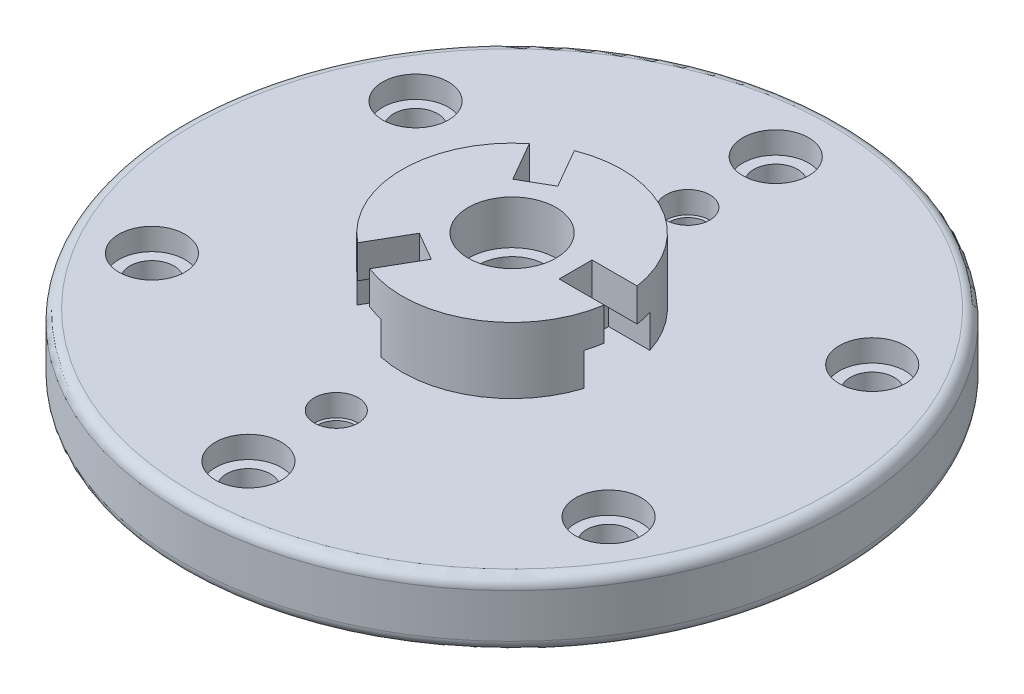
SolidWorks part; units mm, degrees
ref_plane "Front Plane" through (0, 0, 0) normal (0, 0, 1) x (1, 0, 0)
ref_plane "Top Plane" through (0, 0, 0) normal (0, 1, 0) x (1, 0, 0)
ref_plane "Right Plane" through (0, 0, 0) normal (1, 0, 0) x (0, 0, -1)
sketch "Sketch1" plane through (0, 0, 0) normal (0, 1, 0) x (1, 0, 0)
  circle A0 centre (0, 0) radius 30
  dimension "D1" = 60
extrude "Boss-Extrude1" add sketch "Sketch1" along normal blind 50
sketch "Sketch2" plane through (0, 50, 0) normal (0, 1, 0) x (1, 0, 0)
  circle A0 centre (0, 0) radius 60
  dimension "D1" = 120
extrude "Boss-Extrude2" add sketch "Sketch2" along normal blind 20
sketch "Sketch3" plane through (0, 70, 0) normal (0, 1, 0) x (1, 0, 0)
  circle A0 centre (0, 0) radius 150
  dimension "D1" = 300
extrude "Boss-Extrude3" add sketch "Sketch3" along normal blind 30
sketch "Sketch4" plane through (0, 100, 0) normal (0, 1, 0) x (1, 0, 0)
  circle A0 centre (0, 0) radius 50
  dimension "D1" = 100
extrude "Boss-Extrude4" add sketch "Sketch4" along normal blind 30
sketch "Sketch5" plane through (0, 130, 0) normal (0, 1, 0) x (1, 0, 0)
  circle A0 centre (0, 0) radius 15
  dimension "D1" = 30
extrude "Cut-Extrude1" cut sketch "Sketch5" against normal through all
sketch "Sketch6" plane through (0, 130, 0) normal (0, 1, 0) x (1, 0, 0)
  circle A0 centre (0, 0) radius 20
  dimension "D1" = 40
extrude "Cut-Extrude2" cut sketch "Sketch6" against normal blind 20
sketch "Sketch7" plane through (0, 100, 0) normal (0, 1, 0) x (1, 0, 0)
  circle A0 centre (0, 0) radius 120 construction
  circle A1 centre (0, 120) radius 15
  circle A2 centre (0, 120) radius 10
  circle A3 centre (103.923, 60) radius 15
  circle A4 centre (103.923, 60) radius 10
  circle A5 centre (103.923, -60) radius 15
  circle A6 centre (103.923, -60) radius 10
  circle A7 centre (0, -120) radius 15
  circle A8 centre (0, -120) radius 10
  circle A9 centre (-103.923, -60) radius 15
  circle A10 centre (-103.923, -60) radius 10
  circle A11 centre (-103.923, 60) radius 15
  circle A12 centre (-103.923, 60) radius 10
  point P24 (0, 0)
  dimension "D1" = 240
  dimension "D2" = 30
  dimension "D3" = 20
  dimension "D4" = 6
extrude "Cut-Extrude3" cut sketch "Sketch7" against normal blind 10 contours A10 | A9 A10 | A12 | A11 A12 | A2 | A1 A2 | A3 A4 | A4 | A5 A6 | A6 | A7 A8 | A8 region at (-14.5757, 100, -120) region at (0, 100, -120) region at (89.3473, 100, -60) region at (103.923, 100, -60) region at (89.3473, 100, 60) region at (103.923, 100, 60) region at (-14.5757, 100, 120) region at (0, 100, 120) region at (-118.4988, 100, 60) region at (-103.923, 100, 60) region at (-118.4988, 100, -60) region at (-103.923, 100, -60)
extrude "Cut-Extrude4" cut sketch "Sketch7<3>" against normal through all contours A10 | A12 | A2 | A4 | A6 | A8 region at (0, 100, -120) region at (103.923, 100, -60) region at (103.923, 100, 60) region at (0, 100, 120) region at (-103.923, 100, 60) region at (-103.923, 100, -60)
sketch "Sketch7<3>" plane through (0, 100, 0) normal (0, 1, 0) x (1, 0, 0) same geometry as "Sketch7"
sketch "Sketch8" plane through (0, 100, 0) normal (0, 1, 0) x (1, 0, 0)
  line L0 (0, 0) -> (-78.0736, 0) construction
  line L1 (0, 0) -> (0, 67.7311) construction
  circle A0 centre (0, 80) radius 10
  circle A1 centre (0, 80) radius 8.5
  circle A2 centre (0, -80) radius 10
  circle A3 centre (0, -80) radius 8.5
  dimension "D1" = 20
  dimension "D3" = 160
  dimension "D2" = 1.5
extrude "Cut-Extrude6" cut sketch "Sketch8" against normal through all contours A3 | A1 region at (0, 100, -80) region at (0, 100, 80)
extrude "Cut-Extrude7" cut sketch "Sketch8<3>" against normal blind 10 contours A2 A3 | A0 A1 region at (-9.7172, 100, -80) region at (-9.7172, 100, 80)
sketch "Sketch8<3>" plane through (0, 100, 0) normal (0, 1, 0) x (1, 0, 0) same geometry as "Sketch8"
sketch "Sketch10" plane through (0, 130, 0) normal (0, 1, 0) x (1, 0, 0)
  line L0 (0, 0) -> (50, 0) construction
  line L1 (-20.9498, -21.2861) -> (-7.9594, -28.7861)
  line L2 (28.9092, -7.5) -> (61.0908, -7.5)
  line L3 (28.9092, -7.5) -> (28.9092, 7.5)
  line L4 (28.9092, 7.5) -> (61.0908, 7.5)
  line L5 (61.0908, -7.5) -> (61.0908, 7.5)
  line L6 (28.9092, -7.5) -> (61.0908, 7.5) construction
  line L7 (28.9092, 7.5) -> (61.0908, -7.5) construction
  line L8 (-20.9498, -21.2861) -> (-37.0406, -49.1562)
  line L9 (-37.0406, -49.1562) -> (-24.0502, -56.6562)
  line L10 (-7.9594, -28.7861) -> (-24.0502, -56.6562)
  line L11 (-7.9594, 28.7861) -> (-20.9498, 21.2861)
  line L12 (-7.9594, 28.7861) -> (-24.0502, 56.6562)
  line L13 (-24.0502, 56.6562) -> (-37.0406, 49.1562)
  line L14 (-20.9498, 21.2861) -> (-37.0406, 49.1562)
  point P3 (45, 0)
  point P18 (0, 0)
  dimension "D1" = 15
  dimension "D2" = 3
  dimension "D3" = 45
extrude "Cut-Extrude8" cut sketch "Sketch10" against normal up to surface (30 mm away) up to face at (0, 100, 135)
sketch "Sketch11" plane through (0, 100, 0) normal (0, 1, 0) x (1, 0, 0)
  line L0 (28.9092, 7.5) -> (28.9092, -7.5) construction
  line L1 (28.9092, -15) -> (53.5414, -15)
  line L2 (28.9092, -15) -> (28.9092, 15)
  line L3 (28.9092, 15) -> (53.5414, 15)
  line L4 (53.5414, -15) -> (53.5414, 15)
  line L5 (28.9092, -15) -> (53.5414, 15) construction
  line L6 (28.9092, 15) -> (53.5414, -15) construction
  line L7 (-27.445, -17.5361) -> (-1.4642, -32.5361)
  line L8 (-27.445, -17.5361) -> (-39.7611, -38.8682)
  line L9 (-39.7611, -38.8682) -> (-13.7803, -53.8682)
  line L10 (-1.4642, -32.5361) -> (-13.7803, -53.8682)
  line L11 (-1.4642, 32.5361) -> (-27.445, 17.5361)
  line L12 (-1.4642, 32.5361) -> (-13.7803, 53.8682)
  line L13 (-13.7803, 53.8682) -> (-39.7611, 38.8682)
  line L14 (-27.445, 17.5361) -> (-39.7611, 38.8682)
  point P0 (41.2253, 0)
  point P18 (0, 0)
  dimension "D1" = 30
  dimension "D2" = 3
extrude "Cut-Extrude9" cut sketch "Sketch11" along normal blind 15
sketch "Sketch12" plane through (0, 0, 0) normal (0, -1, 0) x (1, 0, 0)
  line L0 (28.75, 20.3044) -> (28.75, -20.3044)
  line L1 (28.75, 0) -> (-28.75, 0) construction
  line L2 (30, 0) -> (30, 15.0234) construction
  line L3 (0, 0) -> (0, -5.7107) construction
  line L4 (-28.75, 20.3044) -> (-28.75, -20.3044)
  circle A0 centre (0, 0) radius 30 construction
  circle A2 centre (0, 0) radius 30
  circle A3 centre (0, 0) radius 30
  circle M6 centre (0, 0) radius 30
  dimension "D1" = 2.5
  dimension "D2" = 0
extrude "Cut-Extrude10" cut sketch "Sketch12" against normal blind 40 contours L4 M6 | L0 M6 region at (29.2509, 0, 0) region at (-29.2509, 0, 0)
fillet "Fillet1" radius 5 2 edges at (0, 100, 150) (0, 70, 150)
